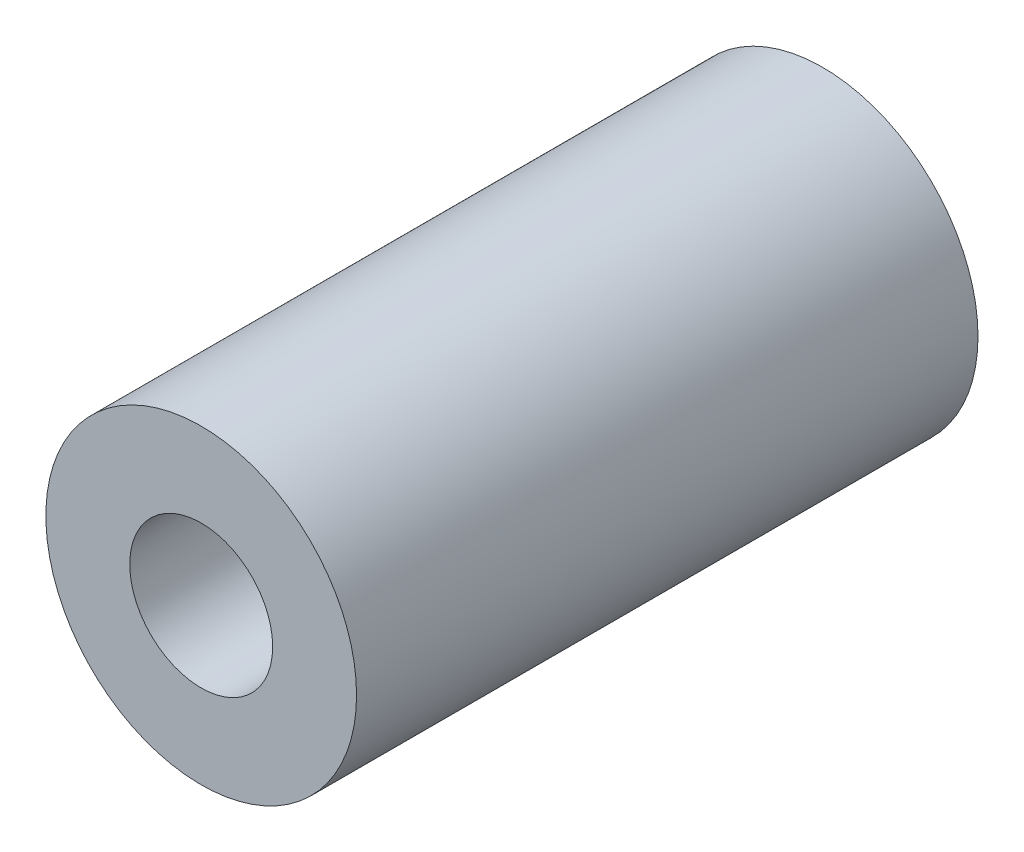
SolidWorks part; units mm, degrees
ref_plane "Front Plane" through (0, 0, 0) normal (0, 0, 1) x (1, 0, 0)
ref_plane "Top Plane" through (0, 0, 0) normal (0, 1, 0) x (1, 0, 0)
ref_plane "Right Plane" through (0, 0, 0) normal (1, 0, 0) x (0, 0, -1)
sketch "Sketch1" plane through (0, 0, 0) normal (0, 0, 1) x (1, 0, 0)
  circle A0 centre (0, 0) radius 3.175
  circle A1 centre (0, 0) radius 1.4605
  dimension "OD" = 6.35
  dimension "ID" = 2.921
extrude "Extrude1" add sketch "Sketch1" along normal mid plane 12.7
sketch "Sketch2" plane through (0, 0, 0) normal (1, 0, 0) x (0, 0, -1)
  line L0 (-6.35, -1.4605) -> (6.35, -1.4605) construction
  line L3 (6.35, 1.4605) -> (-6.35, 1.4605) construction
  line L5 (-6.35, -1.4605) -> (6.35, -1.4605)
  line L6 (6.35, 1.4605) -> (-6.35, 1.4605)
sketch "Sketch4" plane through (0, 0, 6.35) normal (0, 0, 1) x (1, 0, 0)
  line L0 (0, 0) -> (-1.0327, 1.0327)
  line L1 (0, -1.7463) -> (0, 1.7463) construction
  circle A0 centre (0, 0) radius 1.4605 construction
  dimension "D1" = 45
